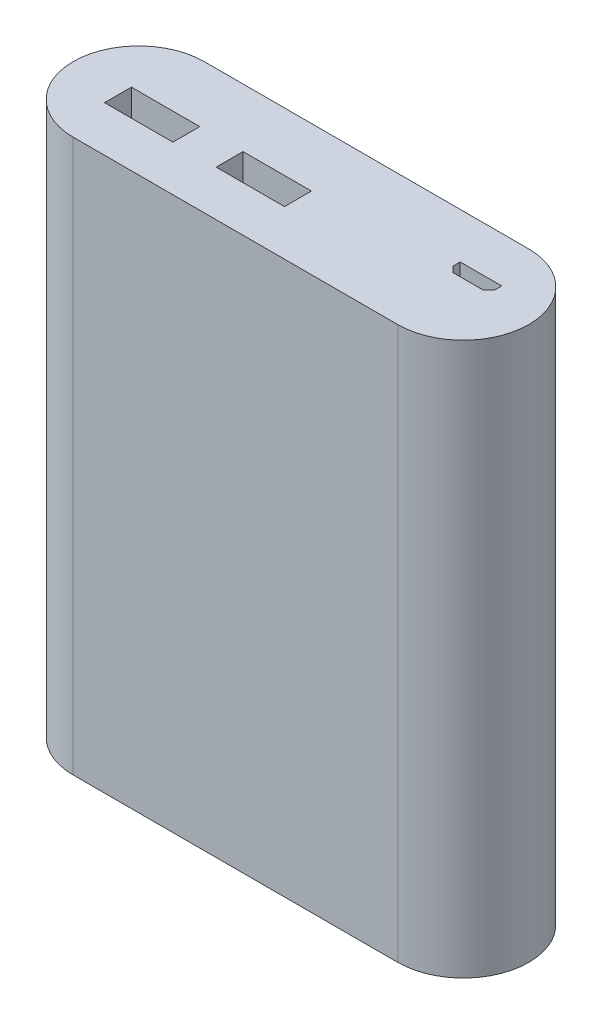
SolidWorks part; units mm, degrees
ref_plane "Front Plane" through (0, 0, 0) normal (0, 0, 1) x (1, 0, 0)
ref_plane "Top Plane" through (0, 0, 0) normal (0, 1, 0) x (1, 0, 0)
ref_plane "Right Plane" through (0, 0, 0) normal (1, 0, 0) x (0, 0, -1)
sketch "Sketch1" plane through (0, 0, 0) normal (0, 1, 0) x (1, 0, 0)
  line L0 (-28.5, 0) -> (28.5, 0) construction
  line L1 (-28.5, 11.5) -> (28.5, 11.5)
  line L2 (-28.5, -11.5) -> (28.5, -11.5)
  arc A0 (-28.5, 11.5) -> (-28.5, -11.5) centre (-28.5, 0) ccw
  arc A1 (28.5, -11.5) -> (28.5, 11.5) centre (28.5, 0) ccw
  point P2 (0, 0)
  dimension "D2" = 80
  dimension "D1" = 23
extrude "Boss-Extrude1" add sketch "Sketch1" along normal blind 97
sketch "Sketch2" plane through (0, 97, 0) normal (0, 1, 0) x (1, 0, 0)
  line L0 (-28.5, -11.5) -> (28.5, -11.5) construction
  line L1 (-31, 1.22) -> (-19, 1.22)
  line L2 (-31, 1.22) -> (-31, -3.5)
  line L3 (-31, -3.5) -> (-19, -3.5)
  line L4 (-19, 1.22) -> (-19, -3.5)
  line L5 (-31, 1.22) -> (-19, -3.5) construction
  line L6 (-31, -3.5) -> (-19, 1.22) construction
  line L7 (0.6, 1.22) -> (0.6, -3.5)
  line L8 (-11.4, 1.22) -> (0.6, 1.22)
  line L9 (-11.4, 1.22) -> (-11.4, -3.5)
  line L10 (-11.4, -3.5) -> (0.6, -3.5)
  line L11 (25.45, 1.25) -> (24.45, 2.25)
  line L12 (24.45, 2.25) -> (24.45, 3.5)
  line L13 (24.45, 3.5) -> (31.75, 3.5)
  line L14 (31.75, 3.5) -> (31.75, 2.25)
  line L15 (31.75, 2.25) -> (30.75, 1.25)
  line L16 (30.75, 1.25) -> (25.45, 1.25)
  line L17 (28.5, 11.5) -> (-28.5, 11.5) construction
  arc A1 (-28.5, 11.5) -> (-28.5, -11.5) centre (-28.5, 0) ccw construction
  arc A2 (28.5, -11.5) -> (28.5, 11.5) centre (28.5, 0) ccw construction
  point P0 (-25, -1.14)
  point P18 (28.1, 3.5)
  point P21 (28.1, 1.25)
  point P27 (29.1275, -1.1)
  point P28 (24.45, 2.3591)
  point P29 (31.75, 1.8273)
  point P30 (-25, -1.14)
  point P31 (-25, -1.14)
  dimension "D1" = 8
  dimension "D2" = 9
  dimension "D3" = 4.72
  dimension "D4" = 12
  dimension "D6" = 7.6
  dimension "D7" = 8
  dimension "D8" = 8.25
  dimension "D9" = 2.25
  dimension "D10" = 7.3
  dimension "D11" = 1.25
  dimension "D5" = 2
extrude "Cut-Extrude1" cut sketch "Sketch2" against normal blind 10
